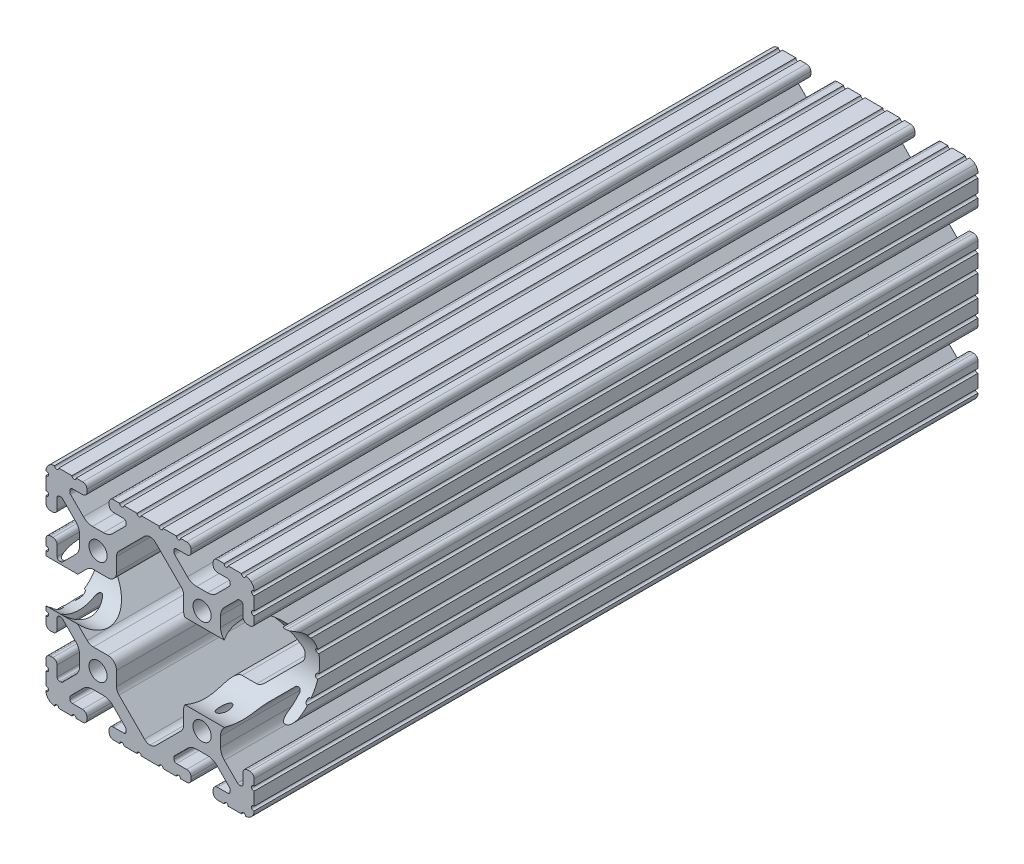
SolidWorks part; units mm, degrees
ref_plane "Front Plane" through (0, 0, 0) normal (0, 0, 1) x (1, 0, 0)
ref_plane "Top Plane" through (0, 0, 0) normal (0, 1, 0) x (1, 0, 0)
ref_plane "Right Plane" through (0, 0, 0) normal (1, 0, 0) x (0, 0, -1)
sketch "Sketch1" plane through (0, 0, 0) normal (0, 0, 1) x (1, 0, 0)
  line L0 (0, 38.1) -> (0, -38.1) construction
  line L1 (-38.1, -38.1) -> (38.1, -38.1) construction
  line L2 (-38.1, -38.1) -> (-38.1, 38.1) construction
  line L3 (-38.1, 38.1) -> (38.1, 38.1) construction
  line L4 (38.1, -38.1) -> (38.1, 38.1) construction
  line L5 (0, 38.1) -> (0, -38.1) construction
  line L6 (-38.1, 0) -> (38.1, 0) construction
  line L7 (-19.05, 19.05) -> (19.05, 19.05) construction
  line L8 (-19.05, 19.05) -> (-19.05, -19.05) construction
  line L9 (-19.05, -19.05) -> (19.05, -19.05) construction
  line L10 (19.05, 19.05) -> (19.05, -19.05) construction
  line L11 (-23.114, 38.1) -> (-23.114, -38.1) construction
  line L12 (-23.114, -38.1) -> (-14.986, 38.1) construction
  line L13 (-14.986, 38.1) -> (-14.986, -38.1) construction
  circle A0 centre (19.05, 19.05) radius 3.3274
  point P0 (0, 0)
  point P9 (0, 0)
  point P12 (-19.05, 0)
  line B0 (-11.3637, -22.8433) -> (-2.0515, -32.1555)
  line B1 (-12.2936, -15.4686) -> (-12.2936, -20.5983)
  line B2 (-20.769, -12.2936) -> (-15.4686, -12.2936)
  line B3 (-31.9021, -2.4756) -> (-23.0141, -11.3637)
  line B4 (-23.0141, 11.3637) -> (-31.9021, 2.4756)
  line B5 (-15.4686, 12.2936) -> (-20.769, 12.2936)
  line B6 (-12.2936, 20.5983) -> (-12.2936, 15.4686)
  line B7 (-2.0515, 32.1555) -> (-11.3637, 22.8433)
  line B8 (11.3637, 22.8433) -> (2.0515, 32.1555)
  line B9 (12.2936, 15.4686) -> (12.2936, 20.5983)
  line B10 (20.769, 12.2936) -> (15.4686, 12.2936)
  line B11 (31.9021, 2.4756) -> (23.0141, 11.3637)
  line B12 (23.0141, -11.3637) -> (31.9021, -2.4756)
  line B13 (15.4686, -12.2936) -> (20.769, -12.2936)
  line B14 (12.2936, -20.5983) -> (12.2936, -15.4686)
  line B15 (2.0515, -32.1555) -> (11.3637, -22.8433)
  line B16 (-4.7773, 38.1) -> (-9.6053, 38.1)
  line B17 (-11.1289, 38.1) -> (-13.4112, 38.1)
  line B18 (-14.986, 36.5252) -> (-14.986, 35.6108)
  line B19 (-13.4112, 34.036) -> (-9.652, 34.036)
  line B20 (-8.763, 33.147) -> (-8.763, 32.4935)
  line B21 (-9.0234, 31.8649) -> (-13.6907, 27.1976)
  line B22 (-17.0493, 25.8064) -> (-21.0507, 25.8064)
  line B23 (-24.4093, 27.1976) -> (-29.1002, 31.8885)
  line B24 (-29.337, 32.7207) -> (-29.337, 33.147)
  line B25 (-28.448, 34.036) -> (-24.6888, 34.036)
  line B26 (-23.114, 35.6108) -> (-23.114, 36.5252)
  line B27 (-24.6888, 38.1) -> (-27.0772, 38.1)
  line B28 (-28.6011, 38.1) -> (-33.4288, 38.1)
  line B29 (-38.1, 33.373) -> (-38.1, 28.5453)
  line B30 (-38.1, 27.0238) -> (-38.1, 24.6302)
  line B31 (-36.5252, 23.0554) -> (-35.6108, 23.0554)
  line B32 (-34.036, 24.6302) -> (-34.036, 28.448)
  line B33 (-33.147, 29.337) -> (-32.6643, 29.337)
  line B34 (-32.0357, 29.0766) -> (-27.1976, 24.2385)
  line B35 (-25.8064, 20.8799) -> (-25.8064, 17.2201)
  line B36 (-27.1976, 13.8615) -> (-31.9489, 9.1101)
  line B37 (-32.7869, 8.763) -> (-33.0603, 8.763)
  line B38 (-34.036, 9.7387) -> (-34.036, 13.4698)
  line B39 (-35.6108, 15.0446) -> (-36.5252, 15.0446)
  line B40 (-38.1, 13.4698) -> (-38.1, 11.075)
  line B41 (-38.1, 9.552) -> (-38.1, 4.7238)
  line B42 (-38.1, 3.2007) -> (-38.1, -3.2007)
  line B43 (-38.1, -4.7238) -> (-38.1, -9.552)
  line B44 (-38.1, -11.075) -> (-38.1, -13.4698)
  line B45 (-36.5252, -15.0446) -> (-35.6108, -15.0446)
  line B46 (-34.036, -13.4698) -> (-34.036, -9.7387)
  line B47 (-33.0603, -8.763) -> (-32.7869, -8.763)
  line B48 (-31.9489, -9.1101) -> (-27.1976, -13.8615)
  line B49 (-25.8064, -17.2201) -> (-25.8064, -20.8799)
  line B50 (-27.1976, -24.2385) -> (-32.0357, -29.0766)
  line B51 (-32.6643, -29.337) -> (-33.147, -29.337)
  line B52 (-34.036, -28.448) -> (-34.036, -24.6302)
  line B53 (-35.6108, -23.0554) -> (-36.5252, -23.0554)
  line B54 (-38.1, -24.6302) -> (-38.1, -27.0238)
  line B55 (-38.1, -28.5453) -> (-38.1, -33.373)
  line B56 (-33.4288, -38.1) -> (-28.6011, -38.1)
  line B57 (-27.0772, -38.1) -> (-24.6888, -38.1)
  line B58 (-23.114, -36.5252) -> (-23.114, -35.6108)
  line B59 (-24.6888, -34.036) -> (-28.448, -34.036)
  line B60 (-29.337, -33.147) -> (-29.337, -32.7207)
  line B61 (-29.1002, -31.8885) -> (-24.4093, -27.1976)
  line B62 (-21.0507, -25.8064) -> (-17.0493, -25.8064)
  line B63 (-13.6907, -27.1976) -> (-9.0234, -31.8649)
  line B64 (-8.763, -32.4935) -> (-8.763, -33.147)
  line B65 (-9.652, -34.036) -> (-13.4112, -34.036)
  line B66 (-14.986, -35.6108) -> (-14.986, -36.5252)
  line B67 (-13.4112, -38.1) -> (-11.1289, -38.1)
  line B68 (-9.6053, -38.1) -> (-4.7773, -38.1)
  line B69 (-3.2537, -38.1) -> (3.2537, -38.1)
  line B70 (4.7773, -38.1) -> (9.6053, -38.1)
  line B71 (11.1289, -38.1) -> (13.4112, -38.1)
  line B72 (14.986, -36.5252) -> (14.986, -35.6108)
  line B73 (13.4112, -34.036) -> (9.652, -34.036)
  line B74 (8.763, -33.147) -> (8.763, -32.4935)
  line B75 (9.0234, -31.8649) -> (13.6907, -27.1976)
  line B76 (17.0493, -25.8064) -> (21.0507, -25.8064)
  line B77 (24.4093, -27.1976) -> (29.1002, -31.8885)
  line B78 (29.337, -32.7207) -> (29.337, -33.147)
  line B79 (28.448, -34.036) -> (24.6888, -34.036)
  line B80 (23.114, -35.6108) -> (23.114, -36.5252)
  line B81 (24.6888, -38.1) -> (27.0772, -38.1)
  line B82 (28.6011, -38.1) -> (33.4288, -38.1)
  line B83 (38.1, -33.373) -> (38.1, -28.5453)
  line B84 (38.1, -27.0238) -> (38.1, -24.6302)
  line B85 (36.5252, -23.0554) -> (35.6108, -23.0554)
  line B86 (34.036, -24.6302) -> (34.036, -28.448)
  line B87 (33.147, -29.337) -> (32.6643, -29.337)
  line B88 (32.0357, -29.0766) -> (27.1976, -24.2385)
  line B89 (25.8064, -20.8799) -> (25.8064, -17.2201)
  line B90 (27.1976, -13.8615) -> (31.9489, -9.1101)
  line B91 (32.7869, -8.763) -> (33.0603, -8.763)
  line B92 (34.036, -9.7387) -> (34.036, -13.4698)
  line B93 (35.6108, -15.0446) -> (36.5252, -15.0446)
  line B94 (38.1, -13.4698) -> (38.1, -11.075)
  line B95 (38.1, -9.552) -> (38.1, -4.7238)
  line B96 (38.1, -3.2007) -> (38.1, 3.2007)
  line B97 (38.1, 4.7238) -> (38.1, 9.552)
  line B98 (38.1, 11.075) -> (38.1, 13.4698)
  line B99 (36.5252, 15.0446) -> (35.6108, 15.0446)
  line B100 (34.036, 13.4698) -> (34.036, 9.7387)
  line B101 (33.0603, 8.763) -> (32.7869, 8.763)
  line B102 (31.9489, 9.1101) -> (27.1976, 13.8615)
  line B103 (25.8064, 17.2201) -> (25.8064, 20.8799)
  line B104 (27.1976, 24.2385) -> (32.0357, 29.0766)
  line B105 (32.6643, 29.337) -> (33.147, 29.337)
  line B106 (34.036, 28.448) -> (34.036, 24.6302)
  line B107 (35.6108, 23.0554) -> (36.5252, 23.0554)
  line B108 (38.1, 24.6302) -> (38.1, 27.0238)
  line B109 (38.1, 28.5453) -> (38.1, 33.373)
  line B110 (33.4288, 38.1) -> (28.6011, 38.1)
  line B111 (27.0772, 38.1) -> (24.6888, 38.1)
  line B112 (23.114, 36.5252) -> (23.114, 35.6108)
  line B113 (24.6888, 34.036) -> (28.448, 34.036)
  line B114 (29.337, 33.147) -> (29.337, 32.7207)
  line B115 (29.1002, 31.8885) -> (24.4093, 27.1976)
  line B116 (21.0507, 25.8064) -> (17.0493, 25.8064)
  line B117 (13.6907, 27.1976) -> (9.0234, 31.8649)
  line B118 (8.763, 32.4935) -> (8.763, 33.147)
  line B119 (9.652, 34.036) -> (13.4112, 34.036)
  line B120 (14.986, 35.6108) -> (14.986, 36.5252)
  line B121 (13.4112, 38.1) -> (11.1289, 38.1)
  line B122 (9.6053, 38.1) -> (4.7773, 38.1)
  line B123 (3.2537, 38.1) -> (-3.2537, 38.1)
  circle B124 centre (-19.05, 19.05) radius 3.3274
  circle B125 centre (-19.05, -19.05) radius 3.3274
  circle B126 centre (19.05, -19.05) radius 3.3274
  circle B127 centre (19.05, 19.05) radius 3.3274
  arc B128 (0, -33.011) -> (2.0515, -32.1555) centre (-0.0139, -30.09) ccw
  arc B129 (-2.0515, -32.1555) -> (0, -33.011) centre (0.0139, -30.09) ccw
  arc B130 (-12.2936, -20.5983) -> (-11.3637, -22.8433) centre (-9.1186, -20.5983) ccw
  arc B131 (-12.2936, -15.4686) -> (-15.4686, -12.2936) centre (-15.4686, -15.4686) ccw
  arc B132 (-23.0141, -11.3637) -> (-20.769, -12.2936) centre (-20.769, -9.1186) ccw
  arc B133 (-32.7287, 0) -> (-31.9021, -2.4756) centre (-29.8367, -0.4102) ccw
  arc B134 (-31.9021, 2.4756) -> (-32.7287, 0) centre (-29.8367, 0.4102) ccw
  arc B135 (-20.769, 12.2936) -> (-23.0141, 11.3637) centre (-20.769, 9.1186) ccw
  arc B136 (-15.4686, 12.2936) -> (-12.2936, 15.4686) centre (-15.4686, 15.4686) ccw
  arc B137 (-11.3637, 22.8433) -> (-12.2936, 20.5983) centre (-9.1186, 20.5983) ccw
  arc B138 (0, 33.011) -> (-2.0515, 32.1555) centre (0.0139, 30.09) ccw
  arc B139 (2.0515, 32.1555) -> (0, 33.011) centre (-0.0139, 30.09) ccw
  arc B140 (12.2936, 20.5983) -> (11.3637, 22.8433) centre (9.1186, 20.5983) ccw
  arc B141 (12.2936, 15.4686) -> (15.4686, 12.2936) centre (15.4686, 15.4686) ccw
  arc B142 (23.0141, 11.3637) -> (20.769, 12.2936) centre (20.769, 9.1186) ccw
  arc B143 (32.7287, 0) -> (31.9021, 2.4756) centre (29.8367, 0.4102) ccw
  arc B144 (31.9021, -2.4756) -> (32.7287, 0) centre (29.8367, -0.4102) ccw
  arc B145 (20.769, -12.2936) -> (23.0141, -11.3637) centre (20.769, -9.1186) ccw
  arc B146 (15.4686, -12.2936) -> (12.2936, -15.4686) centre (15.4686, -15.4686) ccw
  arc B147 (11.3637, -22.8433) -> (12.2936, -20.5983) centre (9.1186, -20.5983) ccw
  arc B148 (-4.7773, 38.1) -> (-3.2537, 38.1) centre (-4.0155, 38.0824) ccw
  arc B149 (-11.1289, 38.1) -> (-9.6053, 38.1) centre (-10.3671, 38.0824) ccw
  arc B150 (-13.4112, 38.1) -> (-14.986, 36.5252) centre (-13.4112, 36.5252) ccw
  arc B151 (-14.986, 35.6108) -> (-13.4112, 34.036) centre (-13.4112, 35.6108) ccw
  arc B152 (-8.763, 33.147) -> (-9.652, 34.036) centre (-9.652, 33.147) ccw
  arc B153 (-9.0234, 31.8649) -> (-8.763, 32.4935) centre (-9.652, 32.4935) ccw
  arc B154 (-17.0493, 25.8064) -> (-13.6907, 27.1976) centre (-17.0493, 30.5562) ccw
  arc B155 (-24.4093, 27.1976) -> (-21.0507, 25.8064) centre (-21.0507, 30.5562) ccw
  arc B156 (-29.337, 32.7207) -> (-29.1002, 31.8885) centre (-28.4716, 32.5172) ccw
  arc B157 (-28.448, 34.036) -> (-29.337, 33.147) centre (-28.448, 33.147) ccw
  arc B158 (-24.6888, 34.036) -> (-23.114, 35.6108) centre (-24.6888, 35.6108) ccw
  arc B159 (-23.114, 36.5252) -> (-24.6888, 38.1) centre (-24.6888, 36.5252) ccw
  arc B160 (-28.6011, 38.1) -> (-27.0772, 38.1) centre (-27.8392, 38.0824) ccw
  arc B161 (-34.9527, 38.1) -> (-33.4288, 38.1) centre (-34.1907, 38.0824) ccw
  arc B162 (-34.9527, 38.1) -> (-37.0861, 37.1826) centre (-34.8521, 34.9266) ccw
  arc B163 (-37.0861, 37.1826) -> (-38.1, 34.8455) centre (-34.925, 34.8566) ccw
  arc B164 (-38.1, 33.373) -> (-38.1, 34.8455) centre (-37.9035, 34.1092) ccw
  arc B165 (-38.1, 27.0238) -> (-38.1, 28.5453) centre (-37.9035, 27.7845) ccw
  arc B166 (-38.1, 24.6302) -> (-36.5252, 23.0554) centre (-36.5252, 24.6302) ccw
  arc B167 (-35.6108, 23.0554) -> (-34.036, 24.6302) centre (-35.6108, 24.6302) ccw
  arc B168 (-33.147, 29.337) -> (-34.036, 28.448) centre (-33.147, 28.448) ccw
  arc B169 (-32.0357, 29.0766) -> (-32.6643, 29.337) centre (-32.6643, 28.448) ccw
  arc B170 (-25.8064, 20.8799) -> (-27.1976, 24.2385) centre (-30.5562, 20.8799) ccw
  arc B171 (-27.1976, 13.8615) -> (-25.8064, 17.2201) centre (-30.5562, 17.2201) ccw
  arc B172 (-32.7869, 8.763) -> (-31.9489, 9.1101) centre (-32.7869, 9.9481) ccw
  arc B173 (-34.036, 9.7387) -> (-33.0603, 8.763) centre (-33.0603, 9.7387) ccw
  arc B174 (-34.036, 13.4698) -> (-35.6108, 15.0446) centre (-35.6108, 13.4698) ccw
  arc B175 (-36.5252, 15.0446) -> (-38.1, 13.4698) centre (-36.5252, 13.4698) ccw
  arc B176 (-38.1, 9.552) -> (-38.1, 11.075) centre (-37.9035, 10.3135) ccw
  arc B177 (-38.1, 3.2007) -> (-38.1, 4.7238) centre (-37.9035, 3.9622) ccw
  arc B178 (-38.1, -4.7238) -> (-38.1, -3.2007) centre (-37.9035, -3.9622) ccw
  arc B179 (-38.1, -11.075) -> (-38.1, -9.552) centre (-37.9035, -10.3135) ccw
  arc B180 (-38.1, -13.4698) -> (-36.5252, -15.0446) centre (-36.5252, -13.4698) ccw
  arc B181 (-35.6108, -15.0446) -> (-34.036, -13.4698) centre (-35.6108, -13.4698) ccw
  arc B182 (-33.0603, -8.763) -> (-34.036, -9.7387) centre (-33.0603, -9.7387) ccw
  arc B183 (-31.9489, -9.1101) -> (-32.7869, -8.763) centre (-32.7869, -9.9481) ccw
  arc B184 (-25.8064, -17.2201) -> (-27.1976, -13.8615) centre (-30.5562, -17.2201) ccw
  arc B185 (-27.1976, -24.2385) -> (-25.8064, -20.8799) centre (-30.5562, -20.8799) ccw
  arc B186 (-32.6643, -29.337) -> (-32.0357, -29.0766) centre (-32.6643, -28.448) ccw
  arc B187 (-34.036, -28.448) -> (-33.147, -29.337) centre (-33.147, -28.448) ccw
  arc B188 (-34.036, -24.6302) -> (-35.6108, -23.0554) centre (-35.6108, -24.6302) ccw
  arc B189 (-36.5252, -23.0554) -> (-38.1, -24.6302) centre (-36.5252, -24.6302) ccw
  arc B190 (-38.1, -28.5453) -> (-38.1, -27.0238) centre (-37.9035, -27.7845) ccw
  arc B191 (-38.1, -34.8455) -> (-38.1, -33.373) centre (-37.9035, -34.1092) ccw
  arc B192 (-38.1, -34.8455) -> (-37.0861, -37.1826) centre (-34.925, -34.8566) ccw
  arc B193 (-37.0861, -37.1826) -> (-34.9527, -38.1) centre (-34.8521, -34.9266) ccw
  arc B194 (-33.4288, -38.1) -> (-34.9527, -38.1) centre (-34.1907, -38.0824) ccw
  arc B195 (-27.0772, -38.1) -> (-28.6011, -38.1) centre (-27.8392, -38.0824) ccw
  arc B196 (-24.6888, -38.1) -> (-23.114, -36.5252) centre (-24.6888, -36.5252) ccw
  arc B197 (-23.114, -35.6108) -> (-24.6888, -34.036) centre (-24.6888, -35.6108) ccw
  arc B198 (-29.337, -33.147) -> (-28.448, -34.036) centre (-28.448, -33.147) ccw
  arc B199 (-29.1002, -31.8885) -> (-29.337, -32.7207) centre (-28.4716, -32.5172) ccw
  arc B200 (-21.0507, -25.8064) -> (-24.4093, -27.1976) centre (-21.0507, -30.5562) ccw
  arc B201 (-13.6907, -27.1976) -> (-17.0493, -25.8064) centre (-17.0493, -30.5562) ccw
  arc B202 (-8.763, -32.4935) -> (-9.0234, -31.8649) centre (-9.652, -32.4935) ccw
  arc B203 (-9.652, -34.036) -> (-8.763, -33.147) centre (-9.652, -33.147) ccw
  arc B204 (-13.4112, -34.036) -> (-14.986, -35.6108) centre (-13.4112, -35.6108) ccw
  arc B205 (-14.986, -36.5252) -> (-13.4112, -38.1) centre (-13.4112, -36.5252) ccw
  arc B206 (-9.6053, -38.1) -> (-11.1289, -38.1) centre (-10.3671, -38.0824) ccw
  arc B207 (-3.2537, -38.1) -> (-4.7773, -38.1) centre (-4.0155, -38.0824) ccw
  arc B208 (4.7773, -38.1) -> (3.2537, -38.1) centre (4.0155, -38.0824) ccw
  arc B209 (11.1289, -38.1) -> (9.6053, -38.1) centre (10.3671, -38.0824) ccw
  arc B210 (13.4112, -38.1) -> (14.986, -36.5252) centre (13.4112, -36.5252) ccw
  arc B211 (14.986, -35.6108) -> (13.4112, -34.036) centre (13.4112, -35.6108) ccw
  arc B212 (8.763, -33.147) -> (9.652, -34.036) centre (9.652, -33.147) ccw
  arc B213 (9.0234, -31.8649) -> (8.763, -32.4935) centre (9.652, -32.4935) ccw
  arc B214 (17.0493, -25.8064) -> (13.6907, -27.1976) centre (17.0493, -30.5562) ccw
  arc B215 (24.4093, -27.1976) -> (21.0507, -25.8064) centre (21.0507, -30.5562) ccw
  arc B216 (29.337, -32.7207) -> (29.1002, -31.8885) centre (28.4716, -32.5172) ccw
  arc B217 (28.448, -34.036) -> (29.337, -33.147) centre (28.448, -33.147) ccw
  arc B218 (24.6888, -34.036) -> (23.114, -35.6108) centre (24.6888, -35.6108) ccw
  arc B219 (23.114, -36.5252) -> (24.6888, -38.1) centre (24.6888, -36.5252) ccw
  arc B220 (28.6011, -38.1) -> (27.0772, -38.1) centre (27.8392, -38.0824) ccw
  arc B221 (34.9527, -38.1) -> (33.4288, -38.1) centre (34.1907, -38.0824) ccw
  arc B222 (34.9527, -38.1) -> (37.0861, -37.1826) centre (34.8521, -34.9266) ccw
  arc B223 (37.0861, -37.1826) -> (38.1, -34.8455) centre (34.925, -34.8566) ccw
  arc B224 (38.1, -33.373) -> (38.1, -34.8455) centre (37.9035, -34.1092) ccw
  arc B225 (38.1, -27.0238) -> (38.1, -28.5453) centre (37.9035, -27.7845) ccw
  arc B226 (38.1, -24.6302) -> (36.5252, -23.0554) centre (36.5252, -24.6302) ccw
  arc B227 (35.6108, -23.0554) -> (34.036, -24.6302) centre (35.6108, -24.6302) ccw
  arc B228 (33.147, -29.337) -> (34.036, -28.448) centre (33.147, -28.448) ccw
  arc B229 (32.0357, -29.0766) -> (32.6643, -29.337) centre (32.6643, -28.448) ccw
  arc B230 (25.8064, -20.8799) -> (27.1976, -24.2385) centre (30.5562, -20.8799) ccw
  arc B231 (27.1976, -13.8615) -> (25.8064, -17.2201) centre (30.5562, -17.2201) ccw
  arc B232 (32.7869, -8.763) -> (31.9489, -9.1101) centre (32.7869, -9.9481) ccw
  arc B233 (34.036, -9.7387) -> (33.0603, -8.763) centre (33.0603, -9.7387) ccw
  arc B234 (34.036, -13.4698) -> (35.6108, -15.0446) centre (35.6108, -13.4698) ccw
  arc B235 (36.5252, -15.0446) -> (38.1, -13.4698) centre (36.5252, -13.4698) ccw
  arc B236 (38.1, -9.552) -> (38.1, -11.075) centre (37.9035, -10.3135) ccw
  arc B237 (38.1, -3.2007) -> (38.1, -4.7238) centre (37.9035, -3.9622) ccw
  arc B238 (38.1, 4.7238) -> (38.1, 3.2007) centre (37.9035, 3.9622) ccw
  arc B239 (38.1, 11.075) -> (38.1, 9.552) centre (37.9035, 10.3135) ccw
  arc B240 (38.1, 13.4698) -> (36.5252, 15.0446) centre (36.5252, 13.4698) ccw
  arc B241 (35.6108, 15.0446) -> (34.036, 13.4698) centre (35.6108, 13.4698) ccw
  arc B242 (33.0603, 8.763) -> (34.036, 9.7387) centre (33.0603, 9.7387) ccw
  arc B243 (31.9489, 9.1101) -> (32.7869, 8.763) centre (32.7869, 9.9481) ccw
  arc B244 (25.8064, 17.2201) -> (27.1976, 13.8615) centre (30.5562, 17.2201) ccw
  arc B245 (27.1976, 24.2385) -> (25.8064, 20.8799) centre (30.5562, 20.8799) ccw
  arc B246 (32.6643, 29.337) -> (32.0357, 29.0766) centre (32.6643, 28.448) ccw
  arc B247 (34.036, 28.448) -> (33.147, 29.337) centre (33.147, 28.448) ccw
  arc B248 (34.036, 24.6302) -> (35.6108, 23.0554) centre (35.6108, 24.6302) ccw
  arc B249 (36.5252, 23.0554) -> (38.1, 24.6302) centre (36.5252, 24.6302) ccw
  arc B250 (38.1, 28.5453) -> (38.1, 27.0238) centre (37.9035, 27.7845) ccw
  arc B251 (38.1, 34.8455) -> (38.1, 33.373) centre (37.9035, 34.1092) ccw
  arc B252 (38.1, 34.8455) -> (37.0861, 37.1826) centre (34.925, 34.8566) ccw
  arc B253 (37.0861, 37.1826) -> (34.9527, 38.1) centre (34.8521, 34.9266) ccw
  arc B254 (33.4288, 38.1) -> (34.9527, 38.1) centre (34.1907, 38.0824) ccw
  arc B255 (27.0772, 38.1) -> (28.6011, 38.1) centre (27.8392, 38.0824) ccw
  arc B256 (24.6888, 38.1) -> (23.114, 36.5252) centre (24.6888, 36.5252) ccw
  arc B257 (23.114, 35.6108) -> (24.6888, 34.036) centre (24.6888, 35.6108) ccw
  arc B258 (29.337, 33.147) -> (28.448, 34.036) centre (28.448, 33.147) ccw
  arc B259 (29.1002, 31.8885) -> (29.337, 32.7207) centre (28.4716, 32.5172) ccw
  arc B260 (21.0507, 25.8064) -> (24.4093, 27.1976) centre (21.0507, 30.5562) ccw
  arc B261 (13.6907, 27.1976) -> (17.0493, 25.8064) centre (17.0493, 30.5562) ccw
  arc B262 (8.763, 32.4935) -> (9.0234, 31.8649) centre (9.652, 32.4935) ccw
  arc B263 (9.652, 34.036) -> (8.763, 33.147) centre (9.652, 33.147) ccw
  arc B264 (13.4112, 34.036) -> (14.986, 35.6108) centre (13.4112, 35.6108) ccw
  arc B265 (14.986, 36.5252) -> (13.4112, 38.1) centre (13.4112, 36.5252) ccw
  arc B266 (9.6053, 38.1) -> (11.1289, 38.1) centre (10.3671, 38.0824) ccw
  arc B267 (3.2537, 38.1) -> (4.7773, 38.1) centre (4.0155, 38.0824) ccw
  dimension "Center Hole Diameter" = 6.6548
  dimension "Rail Width" = 76.2
  dimension "Rail Height" = 76.2
  dimension "T-Slot Width" = 8.128
sketch_block_instance "Block1-1"
sketch_block "Block1"
sketch "Sketch2" plane through (0, 0, 0) normal (1, 0, 0) x (0, 0, -1)
  line L0 (-132.5, 0) -> (132.5, 0) construction
  line L1 (-132.5, 38.1) -> (-132.5, -38.1) construction
  line L2 (-132.5, -38.1) -> (132.5, -38.1) construction
  line L3 (132.5, -38.1) -> (132.5, 38.1) construction
  line L4 (-30.9, 0) -> (-30.9, 38.1) construction
  line L5 (-30.9, 38.1) -> (30.9, 38.1) construction
  line L6 (30.9, 38.1) -> (30.9, 0) construction
  point P5 (30.9, 0)
  point P10 (-30.9, 0)
  dimension "D1" = 101.6
  dimension "Length" = 265
  dimension "D2" = 101.6
sketch "Sketch3" plane through (0, 0, 0) normal (0, 0, 1) x (1, 0, 0)
  line L0 (-11.3637, -22.8433) -> (-2.0515, -32.1555) construction
  line L1 (-12.2936, -15.4686) -> (-12.2936, -20.5983) construction
  line L2 (-20.769, -12.2936) -> (-15.4686, -12.2936) construction
  line L3 (-31.9021, -2.4756) -> (-23.0141, -11.3637) construction
  line L4 (-23.0141, 11.3637) -> (-31.9021, 2.4756) construction
  line L5 (-15.4686, 12.2936) -> (-20.769, 12.2936) construction
  line L6 (-12.2936, 20.5983) -> (-12.2936, 15.4686) construction
  line L7 (-2.0515, 32.1555) -> (-11.3637, 22.8433) construction
  line L8 (11.3637, 22.8433) -> (2.0515, 32.1555) construction
  line L9 (12.2936, 15.4686) -> (12.2936, 20.5983) construction
  line L10 (20.769, 12.2936) -> (15.4686, 12.2936) construction
  line L11 (31.9021, 2.4756) -> (23.0141, 11.3637) construction
  line L12 (23.0141, -11.3637) -> (31.9021, -2.4756) construction
  line L13 (15.4686, -12.2936) -> (20.769, -12.2936) construction
  line L14 (12.2936, -20.5983) -> (12.2936, -15.4686) construction
  line L15 (2.0515, -32.1555) -> (11.3637, -22.8433) construction
  line L16 (34.036, 28.448) -> (34.036, 24.6302) construction
  line L17 (35.6108, 23.0554) -> (36.5252, 23.0554) construction
  line L18 (38.1, 24.6302) -> (38.1, 27.0238) construction
  line L19 (38.1, 28.5453) -> (38.1, 33.373) construction
  line L20 (33.4288, 38.1) -> (28.6011, 38.1) construction
  line L21 (27.0772, 38.1) -> (24.6888, 38.1) construction
  line L22 (23.114, 36.5252) -> (23.114, 35.6108) construction
  line L23 (24.6888, 34.036) -> (28.448, 34.036) construction
  line L24 (29.337, 33.147) -> (29.337, 32.7207) construction
  line L25 (29.1002, 31.8885) -> (24.4093, 27.1976) construction
  line L26 (21.0507, 25.8064) -> (17.0493, 25.8064) construction
  line L27 (13.6907, 27.1976) -> (9.0234, 31.8649) construction
  line L28 (8.763, 32.4935) -> (8.763, 33.147) construction
  line L29 (9.652, 34.036) -> (13.4112, 34.036) construction
  line L30 (14.986, 35.6108) -> (14.986, 36.5252) construction
  line L31 (13.4112, 38.1) -> (11.1289, 38.1) construction
  line L32 (9.6053, 38.1) -> (4.7773, 38.1) construction
  line L33 (3.2537, 38.1) -> (-3.2537, 38.1) construction
  line L34 (-4.7773, 38.1) -> (-9.6053, 38.1) construction
  line L35 (-11.1289, 38.1) -> (-13.4112, 38.1) construction
  line L36 (-14.986, 36.5252) -> (-14.986, 35.6108) construction
  line L37 (-13.4112, 34.036) -> (-9.652, 34.036) construction
  line L38 (-8.763, 33.147) -> (-8.763, 32.4935) construction
  line L39 (-9.0234, 31.8649) -> (-13.6907, 27.1976) construction
  line L40 (-17.0493, 25.8064) -> (-21.0507, 25.8064) construction
  line L41 (-24.4093, 27.1976) -> (-29.1002, 31.8885) construction
  line L42 (-29.337, 32.7207) -> (-29.337, 33.147) construction
  line L43 (-28.448, 34.036) -> (-24.6888, 34.036) construction
  line L44 (-23.114, 35.6108) -> (-23.114, 36.5252) construction
  line L45 (-24.6888, 38.1) -> (-27.0772, 38.1) construction
  line L46 (-28.6011, 38.1) -> (-33.4288, 38.1) construction
  line L47 (-38.1, 33.373) -> (-38.1, 28.5453) construction
  line L48 (-38.1, 27.0238) -> (-38.1, 24.6302) construction
  line L49 (-36.5252, 23.0554) -> (-35.6108, 23.0554) construction
  line L50 (-34.036, 24.6302) -> (-34.036, 28.448) construction
  line L51 (-33.147, 29.337) -> (-32.6643, 29.337) construction
  line L52 (-32.0357, 29.0766) -> (-27.1976, 24.2385) construction
  line L53 (-25.8064, 20.8799) -> (-25.8064, 17.2201) construction
  line L54 (-27.1976, 13.8615) -> (-31.9489, 9.1101) construction
  line L55 (-32.7869, 8.763) -> (-33.0603, 8.763) construction
  line L56 (-34.036, 9.7387) -> (-34.036, 13.4698) construction
  line L57 (-35.6108, 15.0446) -> (-36.5252, 15.0446) construction
  line L58 (-38.1, 13.4698) -> (-38.1, 11.075) construction
  line L59 (-38.1, 9.552) -> (-38.1, 4.7238) construction
  line L60 (-38.1, 3.2007) -> (-38.1, -3.2007) construction
  line L61 (-38.1, -4.7238) -> (-38.1, -9.552) construction
  line L62 (-38.1, -11.075) -> (-38.1, -13.4698) construction
  line L63 (-36.5252, -15.0446) -> (-35.6108, -15.0446) construction
  line L64 (-34.036, -13.4698) -> (-34.036, -9.7387) construction
  line L65 (-33.0603, -8.763) -> (-32.7869, -8.763) construction
  line L66 (-31.9489, -9.1101) -> (-27.1976, -13.8615) construction
  line L67 (-25.8064, -17.2201) -> (-25.8064, -20.8799) construction
  line L68 (-27.1976, -24.2385) -> (-32.0357, -29.0766) construction
  line L69 (-32.6643, -29.337) -> (-33.147, -29.337) construction
  line L70 (-34.036, -28.448) -> (-34.036, -24.6302) construction
  line L71 (-35.6108, -23.0554) -> (-36.5252, -23.0554) construction
  line L72 (-38.1, -24.6302) -> (-38.1, -27.0238) construction
  line L73 (-38.1, -28.5453) -> (-38.1, -33.373) construction
  line L74 (-33.4288, -38.1) -> (-28.6011, -38.1) construction
  line L75 (-27.0772, -38.1) -> (-24.6888, -38.1) construction
  line L76 (-23.114, -36.5252) -> (-23.114, -35.6108) construction
  line L77 (-24.6888, -34.036) -> (-28.448, -34.036) construction
  line L78 (-29.337, -33.147) -> (-29.337, -32.7207) construction
  line L79 (-29.1002, -31.8885) -> (-24.4093, -27.1976) construction
  line L80 (-21.0507, -25.8064) -> (-17.0493, -25.8064) construction
  line L81 (-13.6907, -27.1976) -> (-9.0234, -31.8649) construction
  line L82 (-8.763, -32.4935) -> (-8.763, -33.147) construction
  line L83 (-9.652, -34.036) -> (-13.4112, -34.036) construction
  line L84 (-14.986, -35.6108) -> (-14.986, -36.5252) construction
  line L85 (-13.4112, -38.1) -> (-11.1289, -38.1) construction
  line L86 (-9.6053, -38.1) -> (-4.7773, -38.1) construction
  line L87 (-3.2537, -38.1) -> (3.2537, -38.1) construction
  line L88 (4.7773, -38.1) -> (9.6053, -38.1) construction
  line L89 (11.1289, -38.1) -> (13.4112, -38.1) construction
  line L90 (14.986, -36.5252) -> (14.986, -35.6108) construction
  line L91 (13.4112, -34.036) -> (9.652, -34.036) construction
  line L92 (8.763, -33.147) -> (8.763, -32.4935) construction
  line L93 (9.0234, -31.8649) -> (13.6907, -27.1976) construction
  line L94 (17.0493, -25.8064) -> (21.0507, -25.8064) construction
  line L95 (24.4093, -27.1976) -> (29.1002, -31.8885) construction
  line L96 (29.337, -32.7207) -> (29.337, -33.147) construction
  line L97 (28.448, -34.036) -> (24.6888, -34.036) construction
  line L98 (23.114, -35.6108) -> (23.114, -36.5252) construction
  line L99 (24.6888, -38.1) -> (27.0772, -38.1) construction
  line L100 (28.6011, -38.1) -> (33.4288, -38.1) construction
  line L101 (38.1, -33.373) -> (38.1, -28.5453) construction
  line L102 (38.1, -27.0238) -> (38.1, -24.6302) construction
  line L103 (36.5252, -23.0554) -> (35.6108, -23.0554) construction
  line L104 (34.036, -24.6302) -> (34.036, -28.448) construction
  line L105 (33.147, -29.337) -> (32.6643, -29.337) construction
  line L106 (32.0357, -29.0766) -> (27.1976, -24.2385) construction
  line L107 (25.8064, -20.8799) -> (25.8064, -17.2201) construction
  line L108 (27.1976, -13.8615) -> (31.9489, -9.1101) construction
  line L109 (32.7869, -8.763) -> (33.0603, -8.763) construction
  line L110 (34.036, -9.7387) -> (34.036, -13.4698) construction
  line L111 (35.6108, -15.0446) -> (36.5252, -15.0446) construction
  line L112 (38.1, -13.4698) -> (38.1, -11.075) construction
  line L113 (38.1, -9.552) -> (38.1, -4.7238) construction
  line L114 (38.1, -3.2007) -> (38.1, 3.2007) construction
  line L115 (38.1, 4.7238) -> (38.1, 9.552) construction
  line L116 (38.1, 11.075) -> (38.1, 13.4698) construction
  line L117 (36.5252, 15.0446) -> (35.6108, 15.0446) construction
  line L118 (34.036, 13.4698) -> (34.036, 9.7387) construction
  line L119 (33.0603, 8.763) -> (32.7869, 8.763) construction
  line L120 (31.9489, 9.1101) -> (27.1976, 13.8615) construction
  line L121 (25.8064, 17.2201) -> (25.8064, 20.8799) construction
  line L122 (27.1976, 24.2385) -> (32.0357, 29.0766) construction
  line L123 (32.6643, 29.337) -> (33.147, 29.337) construction
  line L124 (-11.3637, -22.8433) -> (-2.0515, -32.1555)
  line L125 (-12.2936, -15.4686) -> (-12.2936, -20.5983)
  line L126 (-20.769, -12.2936) -> (-15.4686, -12.2936)
  line L127 (-31.9021, -2.4756) -> (-23.0141, -11.3637)
  line L128 (-23.0141, 11.3637) -> (-31.9021, 2.4756)
  line L129 (-15.4686, 12.2936) -> (-20.769, 12.2936)
  line L130 (-12.2936, 20.5983) -> (-12.2936, 15.4686)
  line L131 (-2.0515, 32.1555) -> (-11.3637, 22.8433)
  line L132 (11.3637, 22.8433) -> (2.0515, 32.1555)
  line L133 (12.2936, 15.4686) -> (12.2936, 20.5983)
  line L134 (20.769, 12.2936) -> (15.4686, 12.2936)
  line L135 (31.9021, 2.4756) -> (23.0141, 11.3637)
  line L136 (23.0141, -11.3637) -> (31.9021, -2.4756)
  line L137 (15.4686, -12.2936) -> (20.769, -12.2936)
  line L138 (12.2936, -20.5983) -> (12.2936, -15.4686)
  line L139 (2.0515, -32.1555) -> (11.3637, -22.8433)
  line L140 (34.036, 28.448) -> (34.036, 24.6302)
  line L141 (35.6108, 23.0554) -> (36.5252, 23.0554)
  line L142 (38.1, 24.6302) -> (38.1, 27.0238)
  line L143 (38.1, 28.5453) -> (38.1, 33.373)
  line L144 (33.4288, 38.1) -> (28.6011, 38.1)
  line L145 (27.0772, 38.1) -> (24.6888, 38.1)
  line L146 (23.114, 36.5252) -> (23.114, 35.6108)
  line L147 (24.6888, 34.036) -> (28.448, 34.036)
  line L148 (29.337, 33.147) -> (29.337, 32.7207)
  line L149 (29.1002, 31.8885) -> (24.4093, 27.1976)
  line L150 (21.0507, 25.8064) -> (17.0493, 25.8064)
  line L151 (13.6907, 27.1976) -> (9.0234, 31.8649)
  line L152 (8.763, 32.4935) -> (8.763, 33.147)
  line L153 (9.652, 34.036) -> (13.4112, 34.036)
  line L154 (14.986, 35.6108) -> (14.986, 36.5252)
  line L155 (13.4112, 38.1) -> (11.1289, 38.1)
  line L156 (9.6053, 38.1) -> (4.7773, 38.1)
  line L157 (3.2537, 38.1) -> (-3.2537, 38.1)
  line L158 (-4.7773, 38.1) -> (-9.6053, 38.1)
  line L159 (-11.1289, 38.1) -> (-13.4112, 38.1)
  line L160 (-14.986, 36.5252) -> (-14.986, 35.6108)
  line L161 (-13.4112, 34.036) -> (-9.652, 34.036)
  line L162 (-8.763, 33.147) -> (-8.763, 32.4935)
  line L163 (-9.0234, 31.8649) -> (-13.6907, 27.1976)
  line L164 (-17.0493, 25.8064) -> (-21.0507, 25.8064)
  line L165 (-24.4093, 27.1976) -> (-29.1002, 31.8885)
  line L166 (-29.337, 32.7207) -> (-29.337, 33.147)
  line L167 (-28.448, 34.036) -> (-24.6888, 34.036)
  line L168 (-23.114, 35.6108) -> (-23.114, 36.5252)
  line L169 (-24.6888, 38.1) -> (-27.0772, 38.1)
  line L170 (-28.6011, 38.1) -> (-33.4288, 38.1)
  line L171 (-38.1, 33.373) -> (-38.1, 28.5453)
  line L172 (-38.1, 27.0238) -> (-38.1, 24.6302)
  line L173 (-36.5252, 23.0554) -> (-35.6108, 23.0554)
  line L174 (-34.036, 24.6302) -> (-34.036, 28.448)
  line L175 (-33.147, 29.337) -> (-32.6643, 29.337)
  line L176 (-32.0357, 29.0766) -> (-27.1976, 24.2385)
  line L177 (-25.8064, 20.8799) -> (-25.8064, 17.2201)
  line L178 (-27.1976, 13.8615) -> (-31.9489, 9.1101)
  line L179 (-32.7869, 8.763) -> (-33.0603, 8.763)
  line L180 (-34.036, 9.7387) -> (-34.036, 13.4698)
  line L181 (-35.6108, 15.0446) -> (-36.5252, 15.0446)
  line L182 (-38.1, 13.4698) -> (-38.1, 11.075)
  line L183 (-38.1, 9.552) -> (-38.1, 4.7238)
  line L184 (-38.1, 3.2007) -> (-38.1, -3.2007)
  line L185 (-38.1, -4.7238) -> (-38.1, -9.552)
  line L186 (-38.1, -11.075) -> (-38.1, -13.4698)
  line L187 (-36.5252, -15.0446) -> (-35.6108, -15.0446)
  line L188 (-34.036, -13.4698) -> (-34.036, -9.7387)
  line L189 (-33.0603, -8.763) -> (-32.7869, -8.763)
  line L190 (-31.9489, -9.1101) -> (-27.1976, -13.8615)
  line L191 (-25.8064, -17.2201) -> (-25.8064, -20.8799)
  line L192 (-27.1976, -24.2385) -> (-32.0357, -29.0766)
  line L193 (-32.6643, -29.337) -> (-33.147, -29.337)
  line L194 (-34.036, -28.448) -> (-34.036, -24.6302)
  line L195 (-35.6108, -23.0554) -> (-36.5252, -23.0554)
  line L196 (-38.1, -24.6302) -> (-38.1, -27.0238)
  line L197 (-38.1, -28.5453) -> (-38.1, -33.373)
  line L198 (-33.4288, -38.1) -> (-28.6011, -38.1)
  line L199 (-27.0772, -38.1) -> (-24.6888, -38.1)
  line L200 (-23.114, -36.5252) -> (-23.114, -35.6108)
  line L201 (-24.6888, -34.036) -> (-28.448, -34.036)
  line L202 (-29.337, -33.147) -> (-29.337, -32.7207)
  line L203 (-29.1002, -31.8885) -> (-24.4093, -27.1976)
  line L204 (-21.0507, -25.8064) -> (-17.0493, -25.8064)
  line L205 (-13.6907, -27.1976) -> (-9.0234, -31.8649)
  line L206 (-8.763, -32.4935) -> (-8.763, -33.147)
  line L207 (-9.652, -34.036) -> (-13.4112, -34.036)
  line L208 (-14.986, -35.6108) -> (-14.986, -36.5252)
  line L209 (-13.4112, -38.1) -> (-11.1289, -38.1)
  line L210 (-9.6053, -38.1) -> (-4.7773, -38.1)
  line L211 (-3.2537, -38.1) -> (3.2537, -38.1)
  line L212 (4.7773, -38.1) -> (9.6053, -38.1)
  line L213 (11.1289, -38.1) -> (13.4112, -38.1)
  line L214 (14.986, -36.5252) -> (14.986, -35.6108)
  line L215 (13.4112, -34.036) -> (9.652, -34.036)
  line L216 (8.763, -33.147) -> (8.763, -32.4935)
  line L217 (9.0234, -31.8649) -> (13.6907, -27.1976)
  line L218 (17.0493, -25.8064) -> (21.0507, -25.8064)
  line L219 (24.4093, -27.1976) -> (29.1002, -31.8885)
  line L220 (29.337, -32.7207) -> (29.337, -33.147)
  line L221 (28.448, -34.036) -> (24.6888, -34.036)
  line L222 (23.114, -35.6108) -> (23.114, -36.5252)
  line L223 (24.6888, -38.1) -> (27.0772, -38.1)
  line L224 (28.6011, -38.1) -> (33.4288, -38.1)
  line L225 (38.1, -33.373) -> (38.1, -28.5453)
  line L226 (38.1, -27.0238) -> (38.1, -24.6302)
  line L227 (36.5252, -23.0554) -> (35.6108, -23.0554)
  line L228 (34.036, -24.6302) -> (34.036, -28.448)
  line L229 (33.147, -29.337) -> (32.6643, -29.337)
  line L230 (32.0357, -29.0766) -> (27.1976, -24.2385)
  line L231 (25.8064, -20.8799) -> (25.8064, -17.2201)
  line L232 (27.1976, -13.8615) -> (31.9489, -9.1101)
  line L233 (32.7869, -8.763) -> (33.0603, -8.763)
  line L234 (34.036, -9.7387) -> (34.036, -13.4698)
  line L235 (35.6108, -15.0446) -> (36.5252, -15.0446)
  line L236 (38.1, -13.4698) -> (38.1, -11.075)
  line L237 (38.1, -9.552) -> (38.1, -4.7238)
  line L238 (38.1, -3.2007) -> (38.1, 3.2007)
  line L239 (38.1, 4.7238) -> (38.1, 9.552)
  line L240 (38.1, 11.075) -> (38.1, 13.4698)
  line L241 (36.5252, 15.0446) -> (35.6108, 15.0446)
  line L242 (34.036, 13.4698) -> (34.036, 9.7387)
  line L243 (33.0603, 8.763) -> (32.7869, 8.763)
  line L244 (31.9489, 9.1101) -> (27.1976, 13.8615)
  line L245 (25.8064, 17.2201) -> (25.8064, 20.8799)
  line L246 (27.1976, 24.2385) -> (32.0357, 29.0766)
  line L247 (32.6643, 29.337) -> (33.147, 29.337)
  arc A0 (-2.0515, -32.1555) -> (0, -33.011) centre (0.0139, -30.09) ccw construction
  circle A1 centre (19.05, 19.05) radius 3.3274
  circle A2 centre (19.05, 19.05) radius 3.3274
  arc A3 (-12.2936, -20.5983) -> (-11.3637, -22.8433) centre (-9.1186, -20.5983) ccw construction
  arc A4 (-12.2936, -15.4686) -> (-15.4686, -12.2936) centre (-15.4686, -15.4686) ccw construction
  arc A5 (-23.0141, -11.3637) -> (-20.769, -12.2936) centre (-20.769, -9.1186) ccw construction
  arc A6 (-32.7287, 0) -> (-31.9021, -2.4756) centre (-29.8367, -0.4102) ccw construction
  arc A7 (-31.9021, 2.4756) -> (-32.7287, 0) centre (-29.8367, 0.4102) ccw construction
  arc A8 (-20.769, 12.2936) -> (-23.0141, 11.3637) centre (-20.769, 9.1186) ccw construction
  arc A9 (-15.4686, 12.2936) -> (-12.2936, 15.4686) centre (-15.4686, 15.4686) ccw construction
  arc A10 (-11.3637, 22.8433) -> (-12.2936, 20.5983) centre (-9.1186, 20.5983) ccw construction
  arc A11 (0, 33.011) -> (-2.0515, 32.1555) centre (0.0139, 30.09) ccw construction
  arc A12 (2.0515, 32.1555) -> (0, 33.011) centre (-0.0139, 30.09) ccw construction
  arc A13 (12.2936, 20.5983) -> (11.3637, 22.8433) centre (9.1186, 20.5983) ccw construction
  arc A14 (12.2936, 15.4686) -> (15.4686, 12.2936) centre (15.4686, 15.4686) ccw construction
  arc A15 (23.0141, 11.3637) -> (20.769, 12.2936) centre (20.769, 9.1186) ccw construction
  arc A16 (32.7287, 0) -> (31.9021, 2.4756) centre (29.8367, 0.4102) ccw construction
  arc A17 (31.9021, -2.4756) -> (32.7287, 0) centre (29.8367, -0.4102) ccw construction
  arc A18 (20.769, -12.2936) -> (23.0141, -11.3637) centre (20.769, -9.1186) ccw construction
  arc A19 (15.4686, -12.2936) -> (12.2936, -15.4686) centre (15.4686, -15.4686) ccw construction
  arc A20 (11.3637, -22.8433) -> (12.2936, -20.5983) centre (9.1186, -20.5983) ccw construction
  arc A21 (0, -33.011) -> (2.0515, -32.1555) centre (-0.0139, -30.09) ccw construction
  circle A22 centre (-19.05, 19.05) radius 3.3274 construction
  circle A23 centre (19.05, -19.05) radius 3.3274 construction
  circle A24 centre (-19.05, -19.05) radius 3.3274 construction
  circle A25 centre (19.05, 19.05) radius 3.3274 construction
  arc A26 (34.036, 24.6302) -> (35.6108, 23.0554) centre (35.6108, 24.6302) ccw construction
  arc A27 (36.5252, 23.0554) -> (38.1, 24.6302) centre (36.5252, 24.6302) ccw construction
  arc A28 (38.1, 28.5453) -> (38.1, 27.0238) centre (37.9035, 27.7845) ccw construction
  arc A29 (38.1, 34.8455) -> (38.1, 33.373) centre (37.9035, 34.1092) ccw construction
  arc A30 (38.1, 34.8455) -> (37.0861, 37.1826) centre (34.925, 34.8566) ccw construction
  arc A31 (37.0861, 37.1826) -> (34.9527, 38.1) centre (34.8521, 34.9266) ccw construction
  arc A32 (33.4288, 38.1) -> (34.9527, 38.1) centre (34.1907, 38.0824) ccw construction
  arc A33 (27.0772, 38.1) -> (28.6011, 38.1) centre (27.8392, 38.0824) ccw construction
  arc A34 (24.6888, 38.1) -> (23.114, 36.5252) centre (24.6888, 36.5252) ccw construction
  arc A35 (23.114, 35.6108) -> (24.6888, 34.036) centre (24.6888, 35.6108) ccw construction
  arc A36 (29.337, 33.147) -> (28.448, 34.036) centre (28.448, 33.147) ccw construction
  arc A37 (29.1002, 31.8885) -> (29.337, 32.7207) centre (28.4716, 32.5172) ccw construction
  arc A38 (21.0507, 25.8064) -> (24.4093, 27.1976) centre (21.0507, 30.5562) ccw construction
  arc A39 (13.6907, 27.1976) -> (17.0493, 25.8064) centre (17.0493, 30.5562) ccw construction
  arc A40 (8.763, 32.4935) -> (9.0234, 31.8649) centre (9.652, 32.4935) ccw construction
  arc A41 (9.652, 34.036) -> (8.763, 33.147) centre (9.652, 33.147) ccw construction
  arc A42 (13.4112, 34.036) -> (14.986, 35.6108) centre (13.4112, 35.6108) ccw construction
  arc A43 (14.986, 36.5252) -> (13.4112, 38.1) centre (13.4112, 36.5252) ccw construction
  arc A44 (9.6053, 38.1) -> (11.1289, 38.1) centre (10.3671, 38.0824) ccw construction
  arc A45 (3.2537, 38.1) -> (4.7773, 38.1) centre (4.0155, 38.0824) ccw construction
  arc A46 (-4.7773, 38.1) -> (-3.2537, 38.1) centre (-4.0155, 38.0824) ccw construction
  arc A47 (-11.1289, 38.1) -> (-9.6053, 38.1) centre (-10.3671, 38.0824) ccw construction
  arc A48 (-13.4112, 38.1) -> (-14.986, 36.5252) centre (-13.4112, 36.5252) ccw construction
  arc A49 (-14.986, 35.6108) -> (-13.4112, 34.036) centre (-13.4112, 35.6108) ccw construction
  arc A50 (-8.763, 33.147) -> (-9.652, 34.036) centre (-9.652, 33.147) ccw construction
  arc A51 (-9.0234, 31.8649) -> (-8.763, 32.4935) centre (-9.652, 32.4935) ccw construction
  arc A52 (-17.0493, 25.8064) -> (-13.6907, 27.1976) centre (-17.0493, 30.5562) ccw construction
  arc A53 (-24.4093, 27.1976) -> (-21.0507, 25.8064) centre (-21.0507, 30.5562) ccw construction
  arc A54 (-29.337, 32.7207) -> (-29.1002, 31.8885) centre (-28.4716, 32.5172) ccw construction
  arc A55 (-28.448, 34.036) -> (-29.337, 33.147) centre (-28.448, 33.147) ccw construction
  arc A56 (-24.6888, 34.036) -> (-23.114, 35.6108) centre (-24.6888, 35.6108) ccw construction
  arc A57 (-23.114, 36.5252) -> (-24.6888, 38.1) centre (-24.6888, 36.5252) ccw construction
  arc A58 (-28.6011, 38.1) -> (-27.0772, 38.1) centre (-27.8392, 38.0824) ccw construction
  arc A59 (-34.9527, 38.1) -> (-33.4288, 38.1) centre (-34.1907, 38.0824) ccw construction
  arc A60 (-34.9527, 38.1) -> (-37.0861, 37.1826) centre (-34.8521, 34.9266) ccw construction
  arc A61 (-37.0861, 37.1826) -> (-38.1, 34.8455) centre (-34.925, 34.8566) ccw construction
  arc A62 (-38.1, 33.373) -> (-38.1, 34.8455) centre (-37.9035, 34.1092) ccw construction
  arc A63 (-38.1, 27.0238) -> (-38.1, 28.5453) centre (-37.9035, 27.7845) ccw construction
  arc A64 (-38.1, 24.6302) -> (-36.5252, 23.0554) centre (-36.5252, 24.6302) ccw construction
  arc A65 (-35.6108, 23.0554) -> (-34.036, 24.6302) centre (-35.6108, 24.6302) ccw construction
  arc A66 (-33.147, 29.337) -> (-34.036, 28.448) centre (-33.147, 28.448) ccw construction
  arc A67 (-32.0357, 29.0766) -> (-32.6643, 29.337) centre (-32.6643, 28.448) ccw construction
  arc A68 (-25.8064, 20.8799) -> (-27.1976, 24.2385) centre (-30.5562, 20.8799) ccw construction
  arc A69 (-27.1976, 13.8615) -> (-25.8064, 17.2201) centre (-30.5562, 17.2201) ccw construction
  arc A70 (-32.7869, 8.763) -> (-31.9489, 9.1101) centre (-32.7869, 9.9481) ccw construction
  arc A71 (-34.036, 9.7387) -> (-33.0603, 8.763) centre (-33.0603, 9.7387) ccw construction
  arc A72 (-34.036, 13.4698) -> (-35.6108, 15.0446) centre (-35.6108, 13.4698) ccw construction
  arc A73 (-36.5252, 15.0446) -> (-38.1, 13.4698) centre (-36.5252, 13.4698) ccw construction
  arc A74 (-38.1, 9.552) -> (-38.1, 11.075) centre (-37.9035, 10.3135) ccw construction
  arc A75 (-38.1, 3.2007) -> (-38.1, 4.7238) centre (-37.9035, 3.9622) ccw construction
  arc A76 (-38.1, -4.7238) -> (-38.1, -3.2007) centre (-37.9035, -3.9622) ccw construction
  arc A77 (-38.1, -11.075) -> (-38.1, -9.552) centre (-37.9035, -10.3135) ccw construction
  arc A78 (-38.1, -13.4698) -> (-36.5252, -15.0446) centre (-36.5252, -13.4698) ccw construction
  arc A79 (-35.6108, -15.0446) -> (-34.036, -13.4698) centre (-35.6108, -13.4698) ccw construction
  arc A80 (-33.0603, -8.763) -> (-34.036, -9.7387) centre (-33.0603, -9.7387) ccw construction
  arc A81 (-31.9489, -9.1101) -> (-32.7869, -8.763) centre (-32.7869, -9.9481) ccw construction
  arc A82 (-25.8064, -17.2201) -> (-27.1976, -13.8615) centre (-30.5562, -17.2201) ccw construction
  arc A83 (-27.1976, -24.2385) -> (-25.8064, -20.8799) centre (-30.5562, -20.8799) ccw construction
  arc A84 (-32.6643, -29.337) -> (-32.0357, -29.0766) centre (-32.6643, -28.448) ccw construction
  arc A85 (-34.036, -28.448) -> (-33.147, -29.337) centre (-33.147, -28.448) ccw construction
  arc A86 (-34.036, -24.6302) -> (-35.6108, -23.0554) centre (-35.6108, -24.6302) ccw construction
  arc A87 (-36.5252, -23.0554) -> (-38.1, -24.6302) centre (-36.5252, -24.6302) ccw construction
  arc A88 (-38.1, -28.5453) -> (-38.1, -27.0238) centre (-37.9035, -27.7845) ccw construction
  arc A89 (-38.1, -34.8455) -> (-38.1, -33.373) centre (-37.9035, -34.1092) ccw construction
  arc A90 (-38.1, -34.8455) -> (-37.0861, -37.1826) centre (-34.925, -34.8566) ccw construction
  arc A91 (-37.0861, -37.1826) -> (-34.9527, -38.1) centre (-34.8521, -34.9266) ccw construction
  arc A92 (-33.4288, -38.1) -> (-34.9527, -38.1) centre (-34.1907, -38.0824) ccw construction
  arc A93 (-27.0772, -38.1) -> (-28.6011, -38.1) centre (-27.8392, -38.0824) ccw construction
  arc A94 (-24.6888, -38.1) -> (-23.114, -36.5252) centre (-24.6888, -36.5252) ccw construction
  arc A95 (-23.114, -35.6108) -> (-24.6888, -34.036) centre (-24.6888, -35.6108) ccw construction
  arc A96 (-29.337, -33.147) -> (-28.448, -34.036) centre (-28.448, -33.147) ccw construction
  arc A97 (-29.1002, -31.8885) -> (-29.337, -32.7207) centre (-28.4716, -32.5172) ccw construction
  arc A98 (-21.0507, -25.8064) -> (-24.4093, -27.1976) centre (-21.0507, -30.5562) ccw construction
  arc A99 (-13.6907, -27.1976) -> (-17.0493, -25.8064) centre (-17.0493, -30.5562) ccw construction
  arc A100 (-8.763, -32.4935) -> (-9.0234, -31.8649) centre (-9.652, -32.4935) ccw construction
  arc A101 (-9.652, -34.036) -> (-8.763, -33.147) centre (-9.652, -33.147) ccw construction
  arc A102 (-13.4112, -34.036) -> (-14.986, -35.6108) centre (-13.4112, -35.6108) ccw construction
  arc A103 (-14.986, -36.5252) -> (-13.4112, -38.1) centre (-13.4112, -36.5252) ccw construction
  arc A104 (-9.6053, -38.1) -> (-11.1289, -38.1) centre (-10.3671, -38.0824) ccw construction
  arc A105 (-3.2537, -38.1) -> (-4.7773, -38.1) centre (-4.0155, -38.0824) ccw construction
  arc A106 (4.7773, -38.1) -> (3.2537, -38.1) centre (4.0155, -38.0824) ccw construction
  arc A107 (11.1289, -38.1) -> (9.6053, -38.1) centre (10.3671, -38.0824) ccw construction
  arc A108 (13.4112, -38.1) -> (14.986, -36.5252) centre (13.4112, -36.5252) ccw construction
  arc A109 (14.986, -35.6108) -> (13.4112, -34.036) centre (13.4112, -35.6108) ccw construction
  arc A110 (8.763, -33.147) -> (9.652, -34.036) centre (9.652, -33.147) ccw construction
  arc A111 (9.0234, -31.8649) -> (8.763, -32.4935) centre (9.652, -32.4935) ccw construction
  arc A112 (17.0493, -25.8064) -> (13.6907, -27.1976) centre (17.0493, -30.5562) ccw construction
  arc A113 (24.4093, -27.1976) -> (21.0507, -25.8064) centre (21.0507, -30.5562) ccw construction
  arc A114 (29.337, -32.7207) -> (29.1002, -31.8885) centre (28.4716, -32.5172) ccw construction
  arc A115 (28.448, -34.036) -> (29.337, -33.147) centre (28.448, -33.147) ccw construction
  arc A116 (24.6888, -34.036) -> (23.114, -35.6108) centre (24.6888, -35.6108) ccw construction
  arc A117 (23.114, -36.5252) -> (24.6888, -38.1) centre (24.6888, -36.5252) ccw construction
  arc A118 (28.6011, -38.1) -> (27.0772, -38.1) centre (27.8392, -38.0824) ccw construction
  arc A119 (34.9527, -38.1) -> (33.4288, -38.1) centre (34.1907, -38.0824) ccw construction
  arc A120 (34.9527, -38.1) -> (37.0861, -37.1826) centre (34.8521, -34.9266) ccw construction
  arc A121 (37.0861, -37.1826) -> (38.1, -34.8455) centre (34.925, -34.8566) ccw construction
  arc A122 (38.1, -33.373) -> (38.1, -34.8455) centre (37.9035, -34.1092) ccw construction
  arc A123 (38.1, -27.0238) -> (38.1, -28.5453) centre (37.9035, -27.7845) ccw construction
  arc A124 (38.1, -24.6302) -> (36.5252, -23.0554) centre (36.5252, -24.6302) ccw construction
  arc A125 (35.6108, -23.0554) -> (34.036, -24.6302) centre (35.6108, -24.6302) ccw construction
  arc A126 (33.147, -29.337) -> (34.036, -28.448) centre (33.147, -28.448) ccw construction
  arc A127 (32.0357, -29.0766) -> (32.6643, -29.337) centre (32.6643, -28.448) ccw construction
  arc A128 (25.8064, -20.8799) -> (27.1976, -24.2385) centre (30.5562, -20.8799) ccw construction
  arc A129 (27.1976, -13.8615) -> (25.8064, -17.2201) centre (30.5562, -17.2201) ccw construction
  arc A130 (32.7869, -8.763) -> (31.9489, -9.1101) centre (32.7869, -9.9481) ccw construction
  arc A131 (34.036, -9.7387) -> (33.0603, -8.763) centre (33.0603, -9.7387) ccw construction
  arc A132 (34.036, -13.4698) -> (35.6108, -15.0446) centre (35.6108, -13.4698) ccw construction
  arc A133 (36.5252, -15.0446) -> (38.1, -13.4698) centre (36.5252, -13.4698) ccw construction
  arc A134 (38.1, -9.552) -> (38.1, -11.075) centre (37.9035, -10.3135) ccw construction
  arc A135 (38.1, -3.2007) -> (38.1, -4.7238) centre (37.9035, -3.9622) ccw construction
  arc A136 (38.1, 4.7238) -> (38.1, 3.2007) centre (37.9035, 3.9622) ccw construction
  arc A137 (38.1, 11.075) -> (38.1, 9.552) centre (37.9035, 10.3135) ccw construction
  arc A138 (38.1, 13.4698) -> (36.5252, 15.0446) centre (36.5252, 13.4698) ccw construction
  arc A139 (35.6108, 15.0446) -> (34.036, 13.4698) centre (35.6108, 13.4698) ccw construction
  arc A140 (33.0603, 8.763) -> (34.036, 9.7387) centre (33.0603, 9.7387) ccw construction
  arc A141 (31.9489, 9.1101) -> (32.7869, 8.763) centre (32.7869, 9.9481) ccw construction
  arc A142 (25.8064, 17.2201) -> (27.1976, 13.8615) centre (30.5562, 17.2201) ccw construction
  arc A143 (27.1976, 24.2385) -> (25.8064, 20.8799) centre (30.5562, 20.8799) ccw construction
  arc A144 (32.6643, 29.337) -> (32.0357, 29.0766) centre (32.6643, 28.448) ccw construction
  arc A145 (34.036, 28.448) -> (33.147, 29.337) centre (33.147, 28.448) ccw construction
  arc A146 (-2.0515, -32.1555) -> (0, -33.011) centre (0.0139, -30.09) ccw
  arc A147 (-12.2936, -20.5983) -> (-11.3637, -22.8433) centre (-9.1186, -20.5983) ccw
  arc A148 (-12.2936, -15.4686) -> (-15.4686, -12.2936) centre (-15.4686, -15.4686) ccw
  arc A149 (-23.0141, -11.3637) -> (-20.769, -12.2936) centre (-20.769, -9.1186) ccw
  arc A150 (-32.7287, 0) -> (-31.9021, -2.4756) centre (-29.8367, -0.4102) ccw
  arc A151 (-31.9021, 2.4756) -> (-32.7287, 0) centre (-29.8367, 0.4102) ccw
  arc A152 (-20.769, 12.2936) -> (-23.0141, 11.3637) centre (-20.769, 9.1186) ccw
  arc A153 (-15.4686, 12.2936) -> (-12.2936, 15.4686) centre (-15.4686, 15.4686) ccw
  arc A154 (-11.3637, 22.8433) -> (-12.2936, 20.5983) centre (-9.1186, 20.5983) ccw
  arc A155 (0, 33.011) -> (-2.0515, 32.1555) centre (0.0139, 30.09) ccw
  arc A156 (2.0515, 32.1555) -> (0, 33.011) centre (-0.0139, 30.09) ccw
  arc A157 (12.2936, 20.5983) -> (11.3637, 22.8433) centre (9.1186, 20.5983) ccw
  arc A158 (12.2936, 15.4686) -> (15.4686, 12.2936) centre (15.4686, 15.4686) ccw
  arc A159 (23.0141, 11.3637) -> (20.769, 12.2936) centre (20.769, 9.1186) ccw
  arc A160 (32.7287, 0) -> (31.9021, 2.4756) centre (29.8367, 0.4102) ccw
  arc A161 (31.9021, -2.4756) -> (32.7287, 0) centre (29.8367, -0.4102) ccw
  arc A162 (20.769, -12.2936) -> (23.0141, -11.3637) centre (20.769, -9.1186) ccw
  arc A163 (15.4686, -12.2936) -> (12.2936, -15.4686) centre (15.4686, -15.4686) ccw
  arc A164 (11.3637, -22.8433) -> (12.2936, -20.5983) centre (9.1186, -20.5983) ccw
  arc A165 (0, -33.011) -> (2.0515, -32.1555) centre (-0.0139, -30.09) ccw
  circle A166 centre (-19.05, 19.05) radius 3.3274
  circle A167 centre (19.05, -19.05) radius 3.3274
  circle A168 centre (-19.05, -19.05) radius 3.3274
  circle A169 centre (19.05, 19.05) radius 3.3274
  arc A170 (34.036, 24.6302) -> (35.6108, 23.0554) centre (35.6108, 24.6302) ccw
  arc A171 (36.5252, 23.0554) -> (38.1, 24.6302) centre (36.5252, 24.6302) ccw
  arc A172 (38.1, 28.5453) -> (38.1, 27.0238) centre (37.9035, 27.7845) ccw
  arc A173 (38.1, 34.8455) -> (38.1, 33.373) centre (37.9035, 34.1092) ccw
  arc A174 (38.1, 34.8455) -> (37.0861, 37.1826) centre (34.925, 34.8566) ccw
  arc A175 (37.0861, 37.1826) -> (34.9527, 38.1) centre (34.8521, 34.9266) ccw
  arc A176 (33.4288, 38.1) -> (34.9527, 38.1) centre (34.1907, 38.0824) ccw
  arc A177 (27.0772, 38.1) -> (28.6011, 38.1) centre (27.8392, 38.0824) ccw
  arc A178 (24.6888, 38.1) -> (23.114, 36.5252) centre (24.6888, 36.5252) ccw
  arc A179 (23.114, 35.6108) -> (24.6888, 34.036) centre (24.6888, 35.6108) ccw
  arc A180 (29.337, 33.147) -> (28.448, 34.036) centre (28.448, 33.147) ccw
  arc A181 (29.1002, 31.8885) -> (29.337, 32.7207) centre (28.4716, 32.5172) ccw
  arc A182 (21.0507, 25.8064) -> (24.4093, 27.1976) centre (21.0507, 30.5562) ccw
  arc A183 (13.6907, 27.1976) -> (17.0493, 25.8064) centre (17.0493, 30.5562) ccw
  arc A184 (8.763, 32.4935) -> (9.0234, 31.8649) centre (9.652, 32.4935) ccw
  arc A185 (9.652, 34.036) -> (8.763, 33.147) centre (9.652, 33.147) ccw
  arc A186 (13.4112, 34.036) -> (14.986, 35.6108) centre (13.4112, 35.6108) ccw
  arc A187 (14.986, 36.5252) -> (13.4112, 38.1) centre (13.4112, 36.5252) ccw
  arc A188 (9.6053, 38.1) -> (11.1289, 38.1) centre (10.3671, 38.0824) ccw
  arc A189 (3.2537, 38.1) -> (4.7773, 38.1) centre (4.0155, 38.0824) ccw
  arc A190 (-4.7773, 38.1) -> (-3.2537, 38.1) centre (-4.0155, 38.0824) ccw
  arc A191 (-11.1289, 38.1) -> (-9.6053, 38.1) centre (-10.3671, 38.0824) ccw
  arc A192 (-13.4112, 38.1) -> (-14.986, 36.5252) centre (-13.4112, 36.5252) ccw
  arc A193 (-14.986, 35.6108) -> (-13.4112, 34.036) centre (-13.4112, 35.6108) ccw
  arc A194 (-8.763, 33.147) -> (-9.652, 34.036) centre (-9.652, 33.147) ccw
  arc A195 (-9.0234, 31.8649) -> (-8.763, 32.4935) centre (-9.652, 32.4935) ccw
  arc A196 (-17.0493, 25.8064) -> (-13.6907, 27.1976) centre (-17.0493, 30.5562) ccw
  arc A197 (-24.4093, 27.1976) -> (-21.0507, 25.8064) centre (-21.0507, 30.5562) ccw
  arc A198 (-29.337, 32.7207) -> (-29.1002, 31.8885) centre (-28.4716, 32.5172) ccw
  arc A199 (-28.448, 34.036) -> (-29.337, 33.147) centre (-28.448, 33.147) ccw
  arc A200 (-24.6888, 34.036) -> (-23.114, 35.6108) centre (-24.6888, 35.6108) ccw
  arc A201 (-23.114, 36.5252) -> (-24.6888, 38.1) centre (-24.6888, 36.5252) ccw
  arc A202 (-28.6011, 38.1) -> (-27.0772, 38.1) centre (-27.8392, 38.0824) ccw
  arc A203 (-34.9527, 38.1) -> (-33.4288, 38.1) centre (-34.1907, 38.0824) ccw
  arc A204 (-34.9527, 38.1) -> (-37.0861, 37.1826) centre (-34.8521, 34.9266) ccw
  arc A205 (-37.0861, 37.1826) -> (-38.1, 34.8455) centre (-34.925, 34.8566) ccw
  arc A206 (-38.1, 33.373) -> (-38.1, 34.8455) centre (-37.9035, 34.1092) ccw
  arc A207 (-38.1, 27.0238) -> (-38.1, 28.5453) centre (-37.9035, 27.7845) ccw
  arc A208 (-38.1, 24.6302) -> (-36.5252, 23.0554) centre (-36.5252, 24.6302) ccw
  arc A209 (-35.6108, 23.0554) -> (-34.036, 24.6302) centre (-35.6108, 24.6302) ccw
  arc A210 (-33.147, 29.337) -> (-34.036, 28.448) centre (-33.147, 28.448) ccw
  arc A211 (-32.0357, 29.0766) -> (-32.6643, 29.337) centre (-32.6643, 28.448) ccw
  arc A212 (-25.8064, 20.8799) -> (-27.1976, 24.2385) centre (-30.5562, 20.8799) ccw
  arc A213 (-27.1976, 13.8615) -> (-25.8064, 17.2201) centre (-30.5562, 17.2201) ccw
  arc A214 (-32.7869, 8.763) -> (-31.9489, 9.1101) centre (-32.7869, 9.9481) ccw
  arc A215 (-34.036, 9.7387) -> (-33.0603, 8.763) centre (-33.0603, 9.7387) ccw
  arc A216 (-34.036, 13.4698) -> (-35.6108, 15.0446) centre (-35.6108, 13.4698) ccw
  arc A217 (-36.5252, 15.0446) -> (-38.1, 13.4698) centre (-36.5252, 13.4698) ccw
  arc A218 (-38.1, 9.552) -> (-38.1, 11.075) centre (-37.9035, 10.3135) ccw
  arc A219 (-38.1, 3.2007) -> (-38.1, 4.7238) centre (-37.9035, 3.9622) ccw
  arc A220 (-38.1, -4.7238) -> (-38.1, -3.2007) centre (-37.9035, -3.9622) ccw
  arc A221 (-38.1, -11.075) -> (-38.1, -9.552) centre (-37.9035, -10.3135) ccw
  arc A222 (-38.1, -13.4698) -> (-36.5252, -15.0446) centre (-36.5252, -13.4698) ccw
  arc A223 (-35.6108, -15.0446) -> (-34.036, -13.4698) centre (-35.6108, -13.4698) ccw
  arc A224 (-33.0603, -8.763) -> (-34.036, -9.7387) centre (-33.0603, -9.7387) ccw
  arc A225 (-31.9489, -9.1101) -> (-32.7869, -8.763) centre (-32.7869, -9.9481) ccw
  arc A226 (-25.8064, -17.2201) -> (-27.1976, -13.8615) centre (-30.5562, -17.2201) ccw
  arc A227 (-27.1976, -24.2385) -> (-25.8064, -20.8799) centre (-30.5562, -20.8799) ccw
  arc A228 (-32.6643, -29.337) -> (-32.0357, -29.0766) centre (-32.6643, -28.448) ccw
  arc A229 (-34.036, -28.448) -> (-33.147, -29.337) centre (-33.147, -28.448) ccw
  arc A230 (-34.036, -24.6302) -> (-35.6108, -23.0554) centre (-35.6108, -24.6302) ccw
  arc A231 (-36.5252, -23.0554) -> (-38.1, -24.6302) centre (-36.5252, -24.6302) ccw
  arc A232 (-38.1, -28.5453) -> (-38.1, -27.0238) centre (-37.9035, -27.7845) ccw
  arc A233 (-38.1, -34.8455) -> (-38.1, -33.373) centre (-37.9035, -34.1092) ccw
  arc A234 (-38.1, -34.8455) -> (-37.0861, -37.1826) centre (-34.925, -34.8566) ccw
  arc A235 (-37.0861, -37.1826) -> (-34.9527, -38.1) centre (-34.8521, -34.9266) ccw
  arc A236 (-33.4288, -38.1) -> (-34.9527, -38.1) centre (-34.1907, -38.0824) ccw
  arc A237 (-27.0772, -38.1) -> (-28.6011, -38.1) centre (-27.8392, -38.0824) ccw
  arc A238 (-24.6888, -38.1) -> (-23.114, -36.5252) centre (-24.6888, -36.5252) ccw
  arc A239 (-23.114, -35.6108) -> (-24.6888, -34.036) centre (-24.6888, -35.6108) ccw
  arc A240 (-29.337, -33.147) -> (-28.448, -34.036) centre (-28.448, -33.147) ccw
  arc A241 (-29.1002, -31.8885) -> (-29.337, -32.7207) centre (-28.4716, -32.5172) ccw
  arc A242 (-21.0507, -25.8064) -> (-24.4093, -27.1976) centre (-21.0507, -30.5562) ccw
  arc A243 (-13.6907, -27.1976) -> (-17.0493, -25.8064) centre (-17.0493, -30.5562) ccw
  arc A244 (-8.763, -32.4935) -> (-9.0234, -31.8649) centre (-9.652, -32.4935) ccw
  arc A245 (-9.652, -34.036) -> (-8.763, -33.147) centre (-9.652, -33.147) ccw
  arc A246 (-13.4112, -34.036) -> (-14.986, -35.6108) centre (-13.4112, -35.6108) ccw
  arc A247 (-14.986, -36.5252) -> (-13.4112, -38.1) centre (-13.4112, -36.5252) ccw
  arc A248 (-9.6053, -38.1) -> (-11.1289, -38.1) centre (-10.3671, -38.0824) ccw
  arc A249 (-3.2537, -38.1) -> (-4.7773, -38.1) centre (-4.0155, -38.0824) ccw
  arc A250 (4.7773, -38.1) -> (3.2537, -38.1) centre (4.0155, -38.0824) ccw
  arc A251 (11.1289, -38.1) -> (9.6053, -38.1) centre (10.3671, -38.0824) ccw
  arc A252 (13.4112, -38.1) -> (14.986, -36.5252) centre (13.4112, -36.5252) ccw
  arc A253 (14.986, -35.6108) -> (13.4112, -34.036) centre (13.4112, -35.6108) ccw
  arc A254 (8.763, -33.147) -> (9.652, -34.036) centre (9.652, -33.147) ccw
  arc A255 (9.0234, -31.8649) -> (8.763, -32.4935) centre (9.652, -32.4935) ccw
  arc A256 (17.0493, -25.8064) -> (13.6907, -27.1976) centre (17.0493, -30.5562) ccw
  arc A257 (24.4093, -27.1976) -> (21.0507, -25.8064) centre (21.0507, -30.5562) ccw
  arc A258 (29.337, -32.7207) -> (29.1002, -31.8885) centre (28.4716, -32.5172) ccw
  arc A259 (28.448, -34.036) -> (29.337, -33.147) centre (28.448, -33.147) ccw
  arc A260 (24.6888, -34.036) -> (23.114, -35.6108) centre (24.6888, -35.6108) ccw
  arc A261 (23.114, -36.5252) -> (24.6888, -38.1) centre (24.6888, -36.5252) ccw
  arc A262 (28.6011, -38.1) -> (27.0772, -38.1) centre (27.8392, -38.0824) ccw
  arc A263 (34.9527, -38.1) -> (33.4288, -38.1) centre (34.1907, -38.0824) ccw
  arc A264 (34.9527, -38.1) -> (37.0861, -37.1826) centre (34.8521, -34.9266) ccw
  arc A265 (37.0861, -37.1826) -> (38.1, -34.8455) centre (34.925, -34.8566) ccw
  arc A266 (38.1, -33.373) -> (38.1, -34.8455) centre (37.9035, -34.1092) ccw
  arc A267 (38.1, -27.0238) -> (38.1, -28.5453) centre (37.9035, -27.7845) ccw
  arc A268 (38.1, -24.6302) -> (36.5252, -23.0554) centre (36.5252, -24.6302) ccw
  arc A269 (35.6108, -23.0554) -> (34.036, -24.6302) centre (35.6108, -24.6302) ccw
  arc A270 (33.147, -29.337) -> (34.036, -28.448) centre (33.147, -28.448) ccw
  arc A271 (32.0357, -29.0766) -> (32.6643, -29.337) centre (32.6643, -28.448) ccw
  arc A272 (25.8064, -20.8799) -> (27.1976, -24.2385) centre (30.5562, -20.8799) ccw
  arc A273 (27.1976, -13.8615) -> (25.8064, -17.2201) centre (30.5562, -17.2201) ccw
  arc A274 (32.7869, -8.763) -> (31.9489, -9.1101) centre (32.7869, -9.9481) ccw
  arc A275 (34.036, -9.7387) -> (33.0603, -8.763) centre (33.0603, -9.7387) ccw
  arc A276 (34.036, -13.4698) -> (35.6108, -15.0446) centre (35.6108, -13.4698) ccw
  arc A277 (36.5252, -15.0446) -> (38.1, -13.4698) centre (36.5252, -13.4698) ccw
  arc A278 (38.1, -9.552) -> (38.1, -11.075) centre (37.9035, -10.3135) ccw
  arc A279 (38.1, -3.2007) -> (38.1, -4.7238) centre (37.9035, -3.9622) ccw
  arc A280 (38.1, 4.7238) -> (38.1, 3.2007) centre (37.9035, 3.9622) ccw
  arc A281 (38.1, 11.075) -> (38.1, 9.552) centre (37.9035, 10.3135) ccw
  arc A282 (38.1, 13.4698) -> (36.5252, 15.0446) centre (36.5252, 13.4698) ccw
  arc A283 (35.6108, 15.0446) -> (34.036, 13.4698) centre (35.6108, 13.4698) ccw
  arc A284 (33.0603, 8.763) -> (34.036, 9.7387) centre (33.0603, 9.7387) ccw
  arc A285 (31.9489, 9.1101) -> (32.7869, 8.763) centre (32.7869, 9.9481) ccw
  arc A286 (25.8064, 17.2201) -> (27.1976, 13.8615) centre (30.5562, 17.2201) ccw
  arc A287 (27.1976, 24.2385) -> (25.8064, 20.8799) centre (30.5562, 20.8799) ccw
  arc A288 (32.6643, 29.337) -> (32.0357, 29.0766) centre (32.6643, 28.448) ccw
  arc A289 (34.036, 28.448) -> (33.147, 29.337) centre (33.147, 28.448) ccw
  dimension "D1" = 0
extrude "Boss-Extrude1" add sketch "Sketch3" along normal up to vertex (132.5 mm away) and the other way up to vertex (132.5 mm away) contours A289 L140 A170 L141 A171 L142 A172 L143 A173 A174 A175 A176 L144 A177 L145 A178 L146 A179 L147 A180 L148 A181 L149 A182 L150 A183 L151 A184 L152 A185 L153 A186 L154 A187 L155 A188 L156 A189 L157 A190 L158 A191 L159 A192 L160 A193 L161 A194 L162 A195 L163 region at (34.5376, 29.8386, 0) up to point (0, 0, 132.5) other way up to point (0, 0, -132.5)
sketch "Sketch4" plane through (38.1, 0, 0) normal (1, 0, 0) x (0, 0, -1)
  circle A0 centre (-124.5, 0) radius 11.25 construction
  circle A1 centre (-124.5, 0) radius 11.25
extrude "Cut-Extrude1" cut sketch "Sketch4" against normal through all
sketch "Sketch5" plane through (38.1, 0, 0) normal (1, 0, 0) x (0, 0, -1)
  circle A0 centre (-124.5, 0) radius 14 construction
  circle A1 centre (-124.5, 0) radius 14
  circle A3 centre (-124.5, 0) radius 16
  dimension "D1" = 2
extrude "Cut-Extrude4" cut sketch "Sketch5" against normal blind 30 contours A3 body kept at (34.036, -9.7387, -132.5)
sketch "Sketch6" plane through (38.1, 0, 0) normal (1, 0, 0) x (0, 0, -1)
  circle A0 centre (-124.5, 0) radius 16
sketch "Sketch7" plane through (-38.1, 0, 0) normal (-1, 0, 0) x (0, 0, 1)
  circle A0 centre (124.5, 0) radius 11.25
